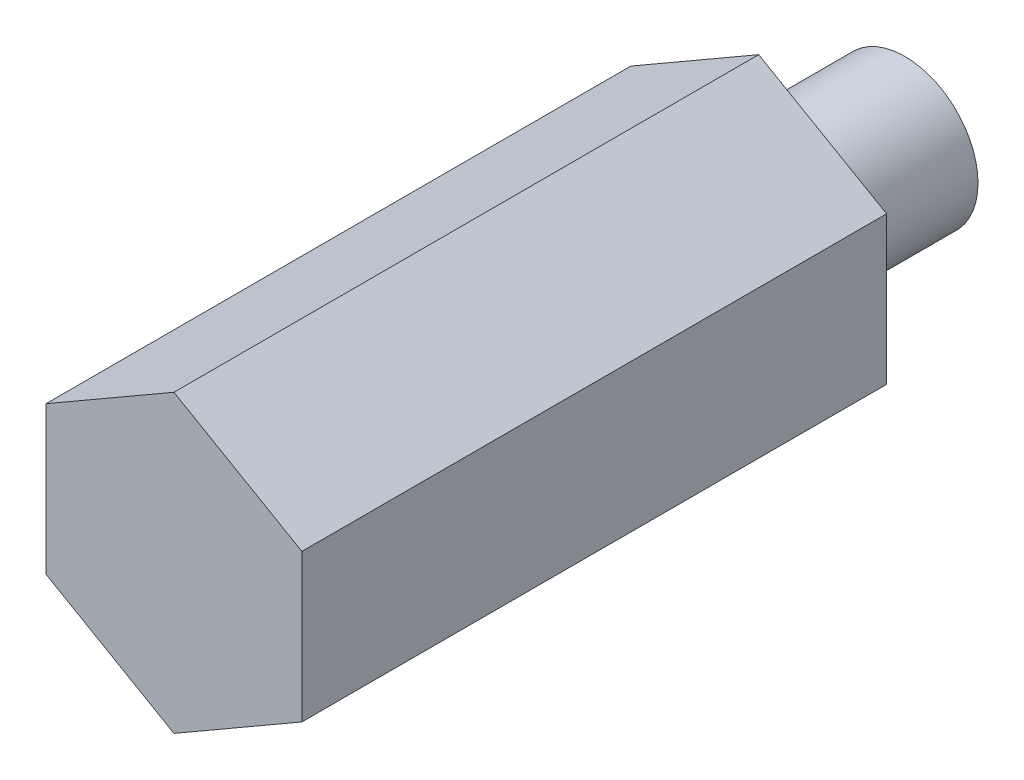
SolidWorks part; units mm, degrees
ref_plane "Front Plane" through (0, 0, 0) normal (0, 0, 1) x (1, 0, 0)
ref_plane "Top Plane" through (0, 0, 0) normal (0, 1, 0) x (1, 0, 0)
ref_plane "Right Plane" through (0, 0, 0) normal (1, 0, 0) x (0, 0, -1)
sketch "Sketch1" plane through (0, 0, 0) normal (0, 0, 1) x (1, 0, 0)
  line L1 (0, 6.4158) -> (-5.5562, 3.2079) construction
  line L2 (-5.5562, 3.2079) -> (-5.5562, -3.2079) construction
  line L3 (-5.5562, -3.2079) -> (0, -6.4158) construction
  line L4 (0, -6.4158) -> (5.5562, -3.2079) construction
  line L5 (5.5562, -3.2079) -> (5.5562, 3.2079) construction
  line L6 (5.5562, 3.2079) -> (0, 6.4158) construction
  circle A2 centre (0, 0) radius 5.5562 construction
  dimension "Width" = 11.1125
sketch "Sketch2" plane through (0, 0, 0) normal (1, 0, 0) x (0, 0, -1)
  line L0 (-12.7, 6.4158) -> (12.7, 6.4158) construction
  point P2 (0, 6.4158)
  point P3 (-15.0813, 6.4158)
  point P4 (15.0813, 6.4158)
  dimension "D2" = 27.7812
  dimension "D1" = 27.7812
sketch "Sketch3" plane through (0, 0, 0) normal (0, 0, 1) x (1, 0, 0)
  line L0 (-5.5562, -3.2079) -> (0, -6.4158) construction
  line L1 (0, -6.4158) -> (5.5562, -3.2079) construction
  line L2 (5.5562, -3.2079) -> (5.5562, 3.2079) construction
  line L3 (5.5562, 3.2079) -> (0, 6.4158) construction
  line L4 (0, 6.4158) -> (-5.5562, 3.2079) construction
  line L5 (-5.5562, 3.2079) -> (-5.5562, -3.2079) construction
  line L6 (-5.5562, -3.2079) -> (0, -6.4158)
  line L7 (0, -6.4158) -> (5.5562, -3.2079)
  line L8 (5.5562, -3.2079) -> (5.5562, 3.2079)
  line L9 (5.5562, 3.2079) -> (0, 6.4158)
  line L10 (0, 6.4158) -> (-5.5562, 3.2079)
  line L11 (-5.5562, 3.2079) -> (-5.5562, -3.2079)
extrude "Boss-Extrude2" add sketch "Sketch3" along normal up to vertex (12.7 mm away) and the other way up to vertex (12.7 mm away) up to point (0, 6.4158, 12.7) other way up to point (0, 6.4158, -12.7)
sketch "Sketch4" plane through (0, 0, -12.7) normal (0, 0, 1) x (1, 0, 0)
  circle A0 centre (0, 0) radius 3.175
  dimension "D1" = 6.35
extrude "Boss-Extrude3" add sketch "Sketch4" against normal blind 6.35
equation "\"D2@Sketch2\" = \"D1@Sketch2\""
equation "\"D1@Sketch2\" = \"Width@Sketch1\" * 2.5"
